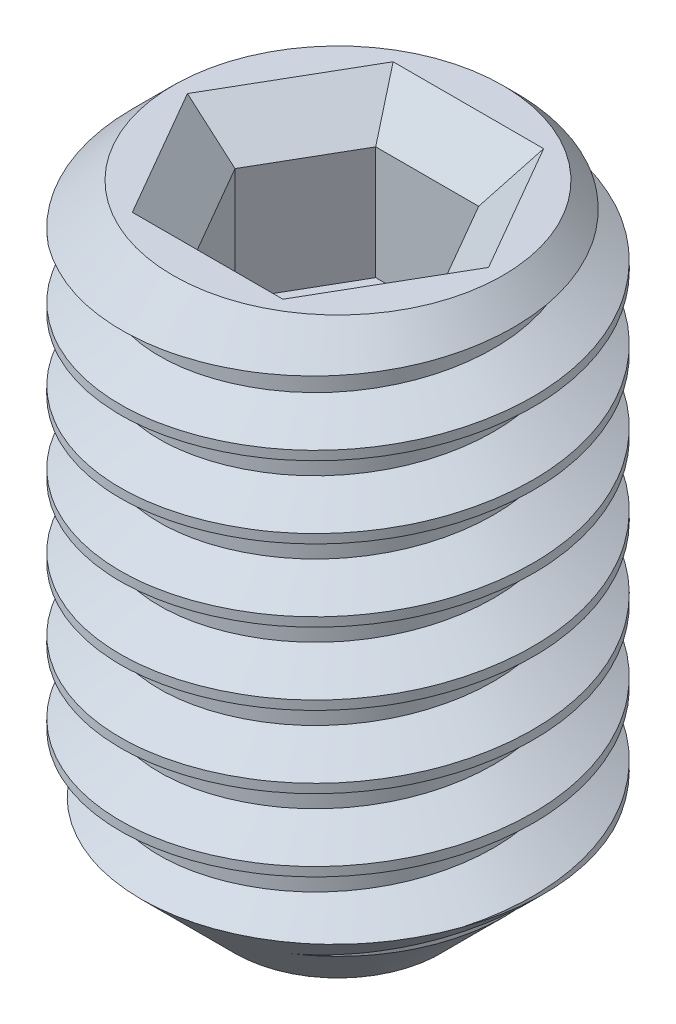
SolidWorks part; units mm, degrees
note: '?' marks a value the reader was unsure of.
material "Gray Cast Iron"
ref_plane "Front Plane" through (0, 0, 0) normal (0, 0, 1) x (1, 0, 0)
ref_plane "Top Plane" through (0, 0, 0) normal (0, 1, 0) x (1, 0, 0)
ref_plane "Right Plane" through (0, 0, 0) normal (1, 0, 0) x (0, 0, -1)
sketch "Sketch1" plane through (0, 0, 0) normal (0, 1, 0) x (1, 0, 0)
  circle A0 centre (0, 0) radius 2
  dimension "D1" = 4
extrude "Boss-Extrude1" add sketch "Sketch1" along normal blind 6
chamfer "Chamfer1" distance 1 angle 45 1 edges at (0, 0, 2)
chamfer "Chamfer2" distance 0.4 angle 45 1 edges at (0, 6, 2)
thread "Thread1" pitch 0.7 start angle 0, offset 0.6, length 0, pitch 0.7, diameter 4
ref_plane "Plane1" through (-2, 6.2, 0) normal (0, 0, 1) x (-1, 0, 0)
sketch "Thread Profile1" plane through (-2, 6.2, 0) normal (0, 0, 1) x (-1, 0, 0)
  line L0 (0, 0) -> (0, 0.7) construction
  line L11 (0, 0) -> (0, 0.6125)
  line L12 (0, 0.6125) -> (-0.3789, 0.3937)
  line L13 (-0.3789, 0.3937) -> (-0.3789, 0.2187)
  line L15 (-0.3789, 0.2187) -> (0, 0)
  line L17 (-0.3789, 0.3062) -> (0, 0.3062) construction
  point P2 (0, 0)
  dimension "Pitch" = 0.7
  dimension "Profile_Angle" = 60
  dimension "Profile_Land" = 0.175
  dimension "Profile_Height" = 0.3789
sketch "Sketch4" plane through (0, 6, 0) normal (0, 1, 0) x (1, 0, 0)
  line L1 (0.5, 0.866) -> (-0.5, 0.866)
  line L2 (-0.5, 0.866) -> (-1, 0)
  line L3 (-1, 0) -> (-0.5, -0.866)
  line L4 (-0.5, -0.866) -> (0.5, -0.866)
  line L5 (0.5, -0.866) -> (1, 0)
  line L6 (1, 0) -> (0.5, 0.866)
  circle A0 centre (0, 0) radius 0.866 construction
  dimension "D1" = 2
extrude "Cut-Extrude1" cut sketch "Sketch4" against normal blind 1.5
chamfer "Chamfer3" distance 0.4 angle 45 6 edges at (0.75, 6, -0.433) (0, 6, -0.866) (-0.75, 6, -0.433) (-0.75, 6, 0.433) (0, 6, 0.866) (0.75, 6, 0.433)
ref_axis "Axis1" through (0, 5.6, 0) along (0, -1, 0)?
